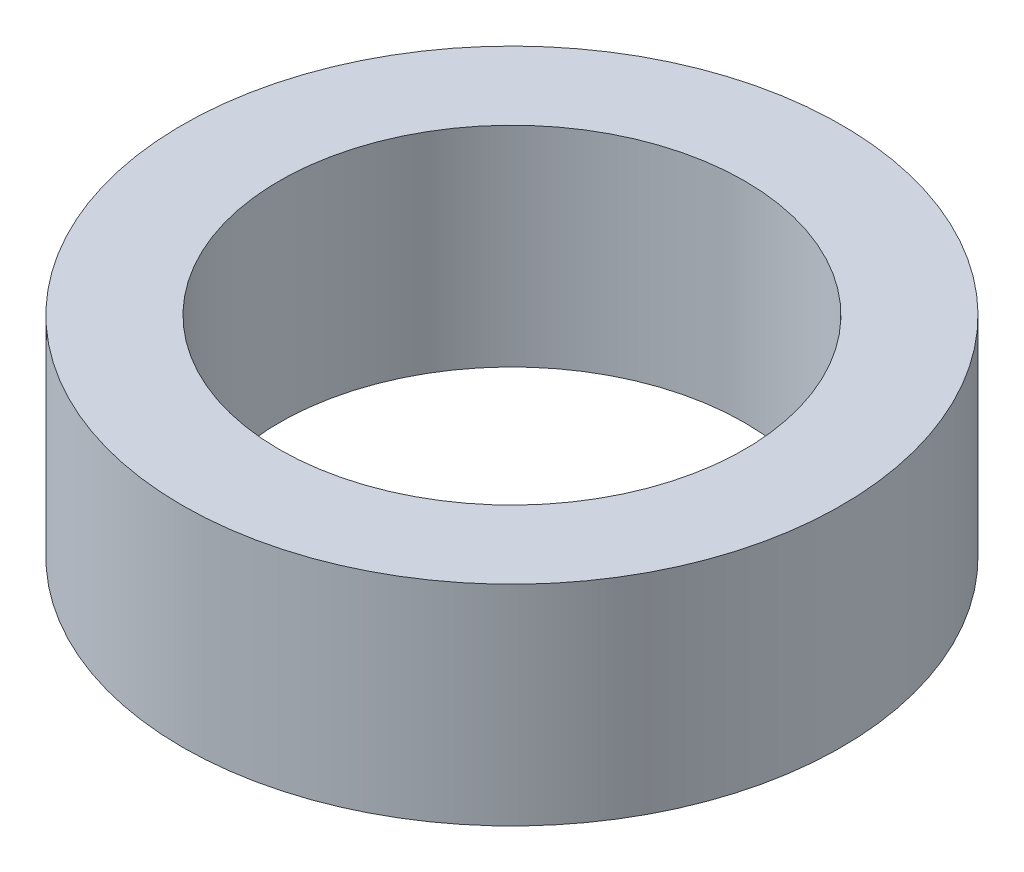
SolidWorks part; units mm, degrees
ref_plane "Front Plane" through (0, 0, 0) normal (0, 0, 1) x (1, 0, 0)
ref_plane "Top Plane" through (0, 0, 0) normal (0, 1, 0) x (1, 0, 0)
ref_plane "Right Plane" through (0, 0, 0) normal (1, 0, 0) x (0, 0, -1)
sketch "Sketch1" plane through (0, 0, 0) normal (0, 1, 0) x (1, 0, 0)
  circle A0 centre (0, 0) radius 42.5
  dimension "FLANGE_OD" = 85
extrude "Boss-Extrude1" add sketch "Sketch1" along normal blind 27
sketch "Sketch2" plane through (0, 0, 0) normal (0, 1, 0) x (1, 0, 0)
  circle A0 centre (0, 0) radius 30
  dimension "BORE_D" = 60
extrude "Cut-Extrude1" cut sketch "Sketch2" along normal through all
sketch "Sketch3" plane through (0, 27, 0) normal (0, 1, 0) x (1, 0, 0)
  circle A0 centre (0, 0) radius 18.3859 construction
  circle A1 centre (-18.3859, 0) radius 2.1874
  dimension "BOLT_D" = 4.3748
  dimension "BOLT_PCD" = 36.7718
extrude "Cut-Extrude2" cut sketch "Sketch3" against normal blind 21.373 rebuild error yes
pattern_circular "CirPattern1" count 4 over 360 rebuild error yes
